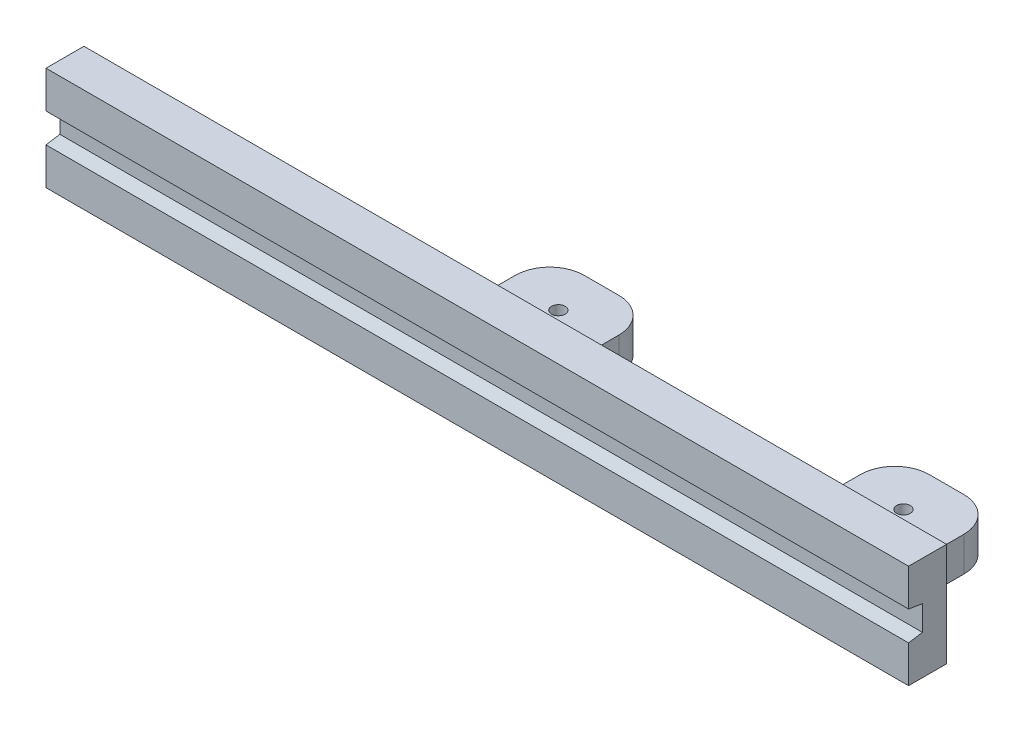
SolidWorks part; units mm, degrees
ref_plane "前基準面" through (0, 0, 0) normal (0, 0, 1) x (1, 0, 0)
ref_plane "上基準面" through (0, 0, 0) normal (0, 1, 0) x (1, 0, 0)
ref_plane "右基準面" through (0, 0, 0) normal (1, 0, 0) x (0, 0, -1)
sketch "草圖1" plane through (0, 0, 0) normal (0, 0, 1) x (1, 0, 0)
  line L0 (0, 0) -> (250, 0)
  line L1 (250, 0) -> (250, 30)
  line L2 (250, 30) -> (0, 30)
  line L3 (0, 30) -> (0, 0)
  dimension "D1" = 30
  dimension "D2" = 250
extrude "填料-伸長1" add sketch "草圖1" along normal blind 11
sketch "草圖4" plane through (0, 0, 0) normal (0, 0, -1) x (-1, 0, 0)
  line L0 (-250, 15) -> (0, 15)
  line L1 (-250, 0) -> (-250, 30) construction
  line L2 (0, 30) -> (0, 0) construction
  line L3 (-125, 30) -> (-125, 0)
  line L4 (-250, 30) -> (0, 30) construction
  line L5 (0, 0) -> (-250, 0) construction
  line L6 (-140, 15) -> (-125, 15)
  line L7 (-125, 15) -> (-110, 15)
  line L8 (-140, 15) -> (-140, 20)
  line L9 (-140, 20) -> (-110, 20)
  line L10 (-110, 20) -> (-110, 15)
  line L11 (-140, 15) -> (-140, 10)
  line L12 (-140, 10) -> (-125, 10)
  line L13 (-125, 10) -> (-110, 10)
  line L14 (-110, 10) -> (-110, 15)
  line L16 (-164.6389, 10) -> (-194.6389, 10)
  line L17 (-164.6389, 10) -> (-164.6389, 20)
  line L18 (-164.6389, 20) -> (-194.6389, 20)
  line L19 (-194.6389, 10) -> (-194.6389, 20)
  line L20 (-164.6389, 10) -> (-194.6389, 20) construction
  line L21 (-164.6389, 20) -> (-194.6389, 10) construction
  point P17 (-179.6389, 15)
  dimension "D1" = 15
  dimension "D2" = 15
  dimension "D3" = 5
  dimension "D4" = 5
  dimension "D5" = 10
  dimension "D6" = 30
extrude "填料-伸長2" add sketch "草圖4" along normal blind 25 contours L11 L12 L3 L0 | L9 L8 L0 L3 | L10 L9 L3 L0 | L13 L14 L0 L3 region at (132.5, 17.5, 0) region at (132.5, 12.5, 0) region at (117.5, 17.5, 0) region at (117.5, 12.5, 0)
sketch "草圖5" plane through (250, 0, 0) normal (1, 0, 0) x (0, 0, -1)
  line L0 (-11, 30) -> (-11, 19.25)
  line L1 (-11, 0) -> (-11, 30) construction
  line L2 (-7, 15) -> (-7, 11.402)
  line L3 (-7, 15) -> (-7, 18.6)
  line L4 (-7, 18.6) -> (-11, 19.25)
  line L5 (-11, 10.75) -> (-11, 0)
  line L6 (-11, 15) -> (0, 15)
  line L7 (0, 30) -> (0, 0) construction
  line L8 (-7, 11.402) -> (-11, 10.75)
  line L9 (-11, 10.75) -> (-11, 19.25)
  line M6 (-11, 30) -> (-11, 0)
  dimension "D1" = 8.5
  dimension "D2" = 10.75
  dimension "D3" = 10.75
  dimension "D4" = 3.6
  dimension "D5" = 3.598
  dimension "D6" = 4
extrude "除料-伸長2" cut sketch "草圖5" against normal through all contours L6 L3 L4 M6 | L8 L2 L6 M6 region at (250, 16.967, 9.0552) region at (250, 13.0335, 9.0554)
sketch "草圖6" plane through (0, 10, 0) normal (0, -1, 0) x (1, 0, 0)
  line L0 (125, 0) -> (125, -25)
  line L1 (250, 0) -> (0, 0) construction
  line L2 (140, -25) -> (110, -25) construction
  line L3 (110, -12.5) -> (140, -12.5)
  line L4 (110, -25) -> (110, 0) construction
  line L5 (140, -25) -> (140, 0) construction
  circle A0 centre (125, -12.5) radius 1.985
  dimension "D1" = 3.97
extrude "除料-伸長3" cut sketch "草圖6" against normal through all contours L3 A0 L0 | L0 A0 L3 | L3 A0 L0 | L0 A0 L3 region at (125.8425, 10, -11.6575) region at (124.1575, 10, -11.6575) region at (125.8425, 10, -13.3425) region at (124.1575, 10, -13.3425)
sketch "草圖7" plane through (0, 10, 0) normal (0, -1, 0) x (1, 0, 0)
  line L0 (125, -14.485) -> (125, -25)
  line L1 (140, -25) -> (110, -25) construction
  circle A0 centre (125, -12.5) radius 1.985 construction
sketch "草圖9" plane through (0, 0, 0) normal (0, 0, -1) x (-1, 0, 0)
  line L1 (-194.6389, 20) -> (-164.6389, 20)
  line L2 (-194.6389, 20) -> (-194.6389, 10)
  line L3 (-194.6389, 10) -> (-164.6389, 10)
  line L4 (-164.6389, 20) -> (-164.6389, 10)
  line L5 (-194.6389, 20) -> (-164.6389, 10) construction
  line L6 (-194.6389, 10) -> (-164.6389, 20) construction
  point P0 (-179.6389, 15)
sketch "草圖11" plane through (0, 0, 0) normal (0, 0, -1) x (-1, 0, 0)
  line L0 (-125, 15) -> (-225, 15)
  line L1 (-250, 15) -> (0, 15) construction
  line L3 (-240, 10) -> (-210, 10)
  line L4 (-240, 10) -> (-240, 20)
  line L5 (-240, 20) -> (-210, 20)
  line L6 (-210, 10) -> (-210, 20)
  line L7 (-240, 10) -> (-210, 20) construction
  line L8 (-240, 20) -> (-210, 10) construction
  dimension "D1" = 100
  dimension "D2" = 10
  dimension "D3" = 30
extrude "填料-伸長4" add sketch "草圖11" along normal blind 25 contours L3 L6 L5 L4 region at (239.6838, 15, 0)
sketch "草圖12" plane through (0, 20, 0) normal (0, 1, 0) x (1, 0, 0)
  line L0 (240, 12.5) -> (210, 12.5)
  line L1 (240, 25) -> (240, 0) construction
  line L2 (210, 25) -> (210, 0) construction
  circle A0 centre (225, 12.5) radius 1.985
  dimension "D1" = 3.97
extrude "除料-伸長5" cut sketch "草圖12" against normal through all contours A0
fillet "圓角1" radius 10 4 edges at (110, 15, -25) (140, 15, -25) (210, 15, -25) (240, 15, -25)
